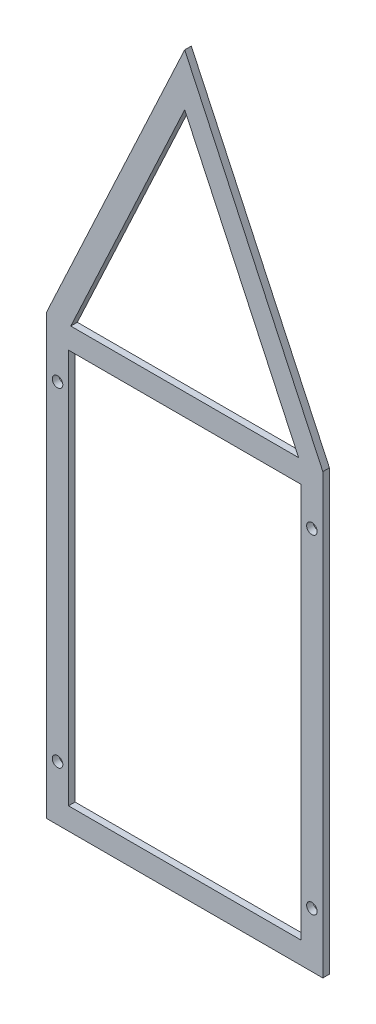
SolidWorks part; units mm, degrees
ref_plane "Front Plane" through (0, 0, 0) normal (0, 0, 1) x (1, 0, 0)
ref_plane "Top Plane" through (0, 0, 0) normal (0, 1, 0) x (1, 0, 0)
ref_plane "Right Plane" through (0, 0, 0) normal (1, 0, 0) x (0, 0, -1)
sketch "Sketch1" plane through (0, 0, 0) normal (0, 0, 1) x (1, 0, 0)
  line L0 (-53, -90) -> (53, -90)
  line L1 (-63, -100) -> (63, -100)
  line L2 (-63, -100) -> (-63, 100)
  line L3 (-63, 100) -> (63, 100)
  line L4 (63, -100) -> (63, 100)
  line L5 (-63, -100) -> (63, 100) construction
  line L6 (-63, 100) -> (63, -100) construction
  line L7 (53, -90) -> (53, 90)
  line L8 (-53, 90) -> (53, 90)
  line L9 (-53, -90) -> (-53, 90)
  point P0 (0, 0)
  dimension "FrameWidth" = 126
  dimension "FrameLength" = 200
  dimension "RibThickness" = 10
extrude "Rectangle Rib" add sketch "Sketch1" along normal mid plane 3
sketch "Sketch2" plane through (0, 0, 1.5) normal (0, 0, 1) x (1, 0, 0)
  line L0 (-63, 100) -> (0, 235.1039)
  line L1 (0, 235.1039) -> (63, 100)
  line L2 (63, 100) -> (51.9662, 100)
  line L3 (63, 100) -> (-63, 100) construction
  line L4 (51.9662, 100) -> (0, 211.4419)
  line L5 (0, 211.4419) -> (-51.9662, 100)
  line L6 (-51.9662, 100) -> (-63, 100)
  line L7 (0, 235.1039) -> (0, 100) construction
  dimension "HalfAngle" = 25
  dimension "TopRibThickness" = 10
extrude "Triangle Rib" add sketch "Sketch2" against normal up to surface (3 mm away) up to face at (0, 0, -1.5)
sketch "Sketch3" plane through (0, 0, 1.5) normal (0, 0, 1) x (1, 0, 0)
  line L0 (-63, 90) -> (-58, 90) construction
  line L1 (-63, 100) -> (-63, -100) construction
  line L2 (-58, 90) -> (-53, 90) construction
  line L3 (-58, 90) -> (-58, 75) construction
  dimension "ScrewEdgeOffset" = 5
  dimension "ScrewTopOffset" = 15
hole_wizard "M4 Clearance Hole1" positions "Sketch4" profile "Sketch5" hole size "M4" standard "ANSI Metric" end condition up to next
sketch "Sketch4" plane through (0, 0, 1.5) normal (0, 0, 1) x (1, 0, 0)
  point P0 (-58, 75)
sketch "Sketch5" plane through (-58, 75, 1.5) normal (1, 0, 0) x (0, -1, 0)
  line L0 (0, 0) -> (0, 3)
  line L1 (0, 3) -> (2.4, 3)
  line L2 (2.4, 3) -> (2.4, 0)
  line L5 (2.4, 0) -> (0, 0)
  line L11 (0, -6.35) -> (0, 107.95) construction
  dimension "Thru Hole Dia." = 4.8
  dimension "Thru Hole Depth" = 3
mirror "Mirror1" about plane through (0, 0, 0) normal (0, 1, 0) of "M4 Clearance Hole1" second plane through (0, 0, 0) second plane normal (1, 0, 0)
equation "\"FrameWidth\"= 3.30276"
